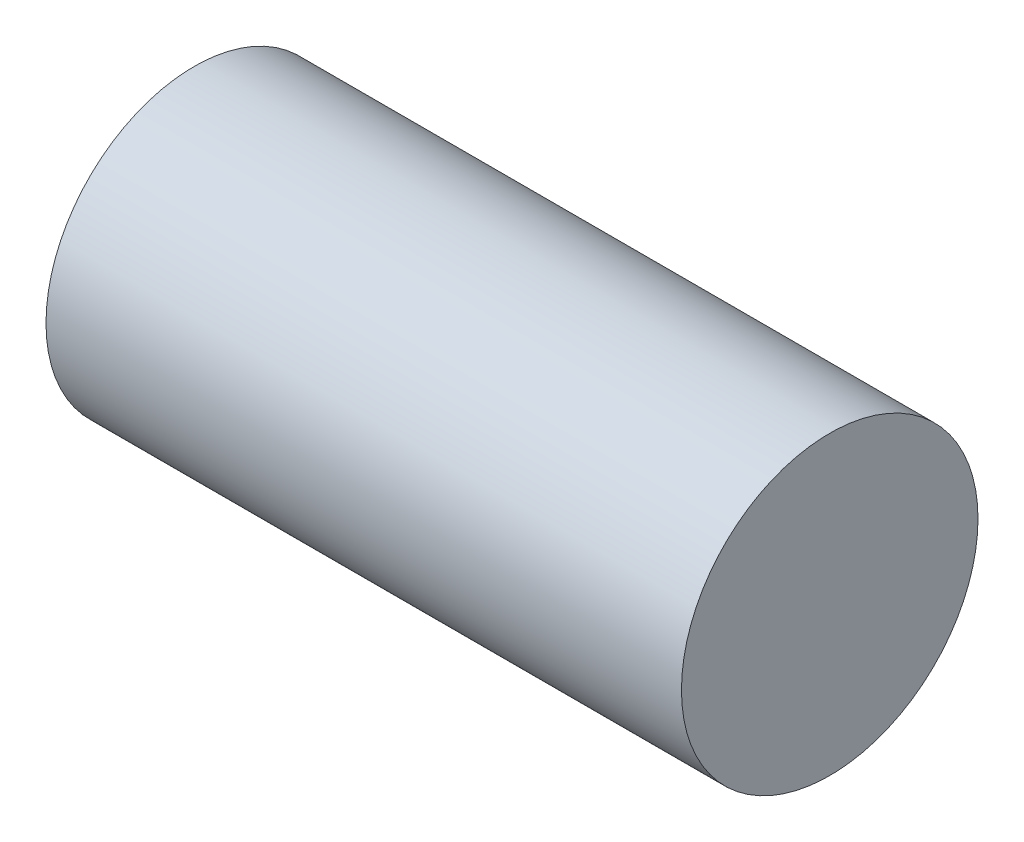
SolidWorks part; units mm, degrees
ref_plane "Front Plane" through (0, 0, 0) normal (0, 0, 1) x (1, 0, 0)
ref_plane "Top Plane" through (0, 0, 0) normal (0, 1, 0) x (1, 0, 0)
ref_plane "Right Plane" through (0, 0, 0) normal (1, 0, 0) x (0, 0, -1)
sketch "Sketch1" plane through (0, 0, 0) normal (1, 0, 0) x (0, 0, -1)
  circle A0 centre (0, 0) radius 7
  dimension "D1" = 14
extrude "Boss-Extrude1" add sketch "Sketch1" along normal blind 30
sketch "Sketch2" plane through (0, 0, 0) normal (-1, 0, 0) x (0, 0, 1)
  point P0 (0, 0)
